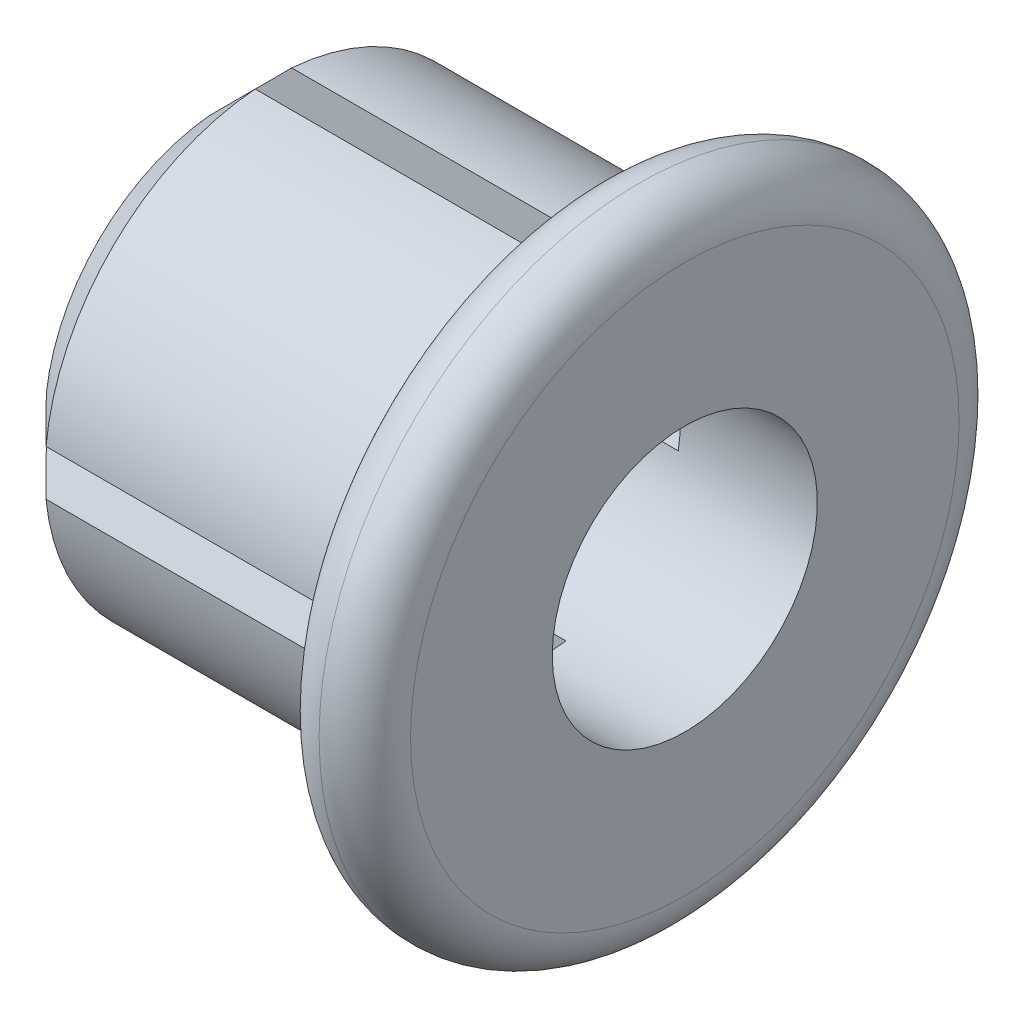
SolidWorks part; units mm, degrees
ref_plane "Front" through (0, 0, 0) normal (0, 0, 1) x (1, 0, 0)
ref_plane "Top" through (0, 0, 0) normal (0, 1, 0) x (1, 0, 0)
ref_plane "Right" through (0, 0, 0) normal (1, 0, 0) x (0, 0, -1)
sketch "Эскиз1" plane through (0, 0, 0) normal (0, 0, 1) x (1, 0, 0)
  line L0 (0, 0) -> (10, 0) construction
  line L1 (10, 2.9) -> (10, 7)
  line L2 (10, 7) -> (8, 7)
  line L3 (8, 7) -> (8, 5)
  line L4 (8, 5) -> (0, 5)
  line L5 (0, 5) -> (0, 2.9)
  line L6 (0, 2.9) -> (10, 2.9)
  dimension "D1" = 2.9
  dimension "D2" = 5
  dimension "D3" = 7
  dimension "D4" = 2
  dimension "D5" = 10
revolve "Повернуть1" add sketch "Эскиз1" angle 360 about L0
chamfer "Фаска1" distance 1 angle 45 1 edges at (0, 0, 5)
fillet "Скругление1" radius 1 2 edges at (10, 0, 7) (8, 0, 7)
sketch "Эскиз2" plane through (0, 0, 0) normal (-1, 0, 0) x (0, 0, 1)
  line L1 (-6, -0.5) -> (-0.3995, -0.5)
  line L2 (-6, -0.5) -> (-6, 0.5)
  line L3 (-6, 0.5) -> (-0.3995, 0.5)
  line L4 (6, -0.5) -> (6, 0.5)
  line L7 (-0.3995, -5.9867) -> (0.3995, -5.9867)
  line L8 (-0.3995, -5.9867) -> (-0.3995, -0.5)
  line L9 (-0.3995, 5.9867) -> (0.3995, 5.9867)
  line L10 (0.3995, -5.9867) -> (0.3995, -0.5)
  line L16 (0.3995, 0.5) -> (0.3995, 5.9867)
  line L17 (-0.3995, 0.5) -> (-0.3995, 5.9867)
  line L18 (0.3995, 0.5) -> (6, 0.5)
  line L19 (0.3995, -0.5) -> (6, -0.5)
  circle A0 centre (0, 0) radius 6 construction
  point P0 (0, 0)
  point P5 (0, 0)
extrude "Вырез-Вытянуть1" cut sketch "Эскиз2" against normal blind 7
